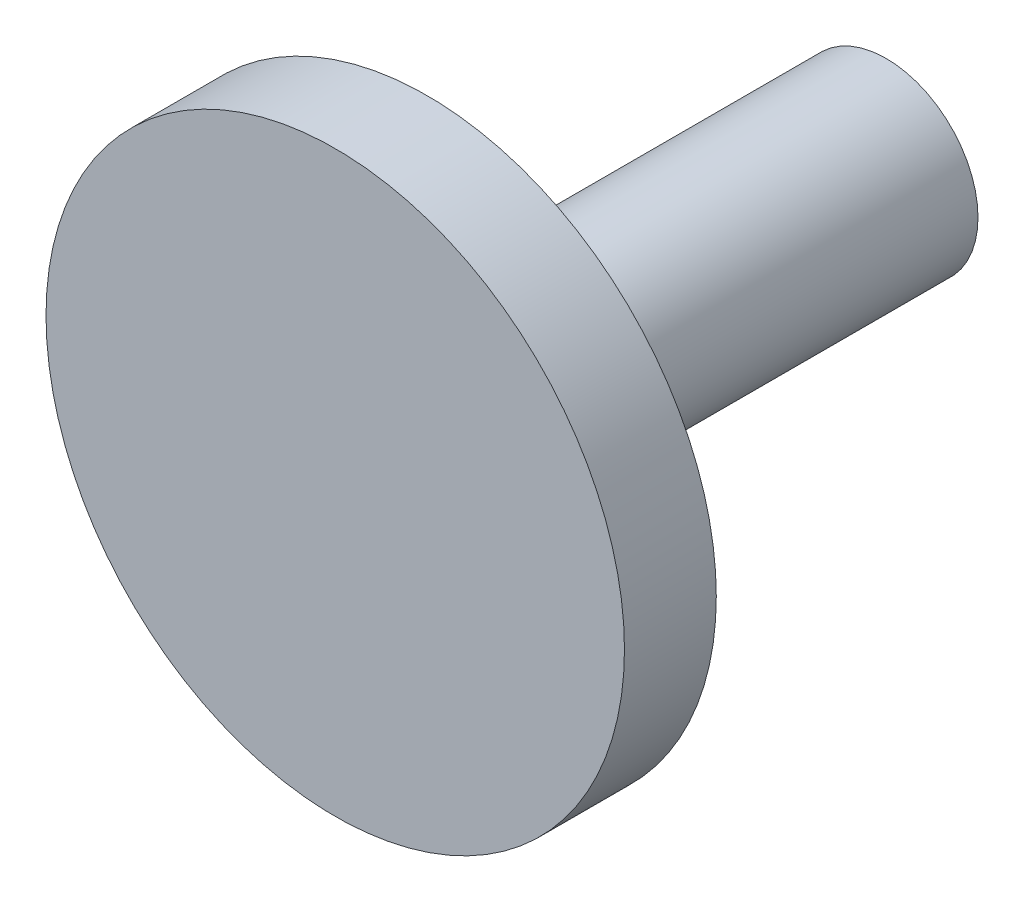
SolidWorks part; units mm, degrees
ref_plane "Front Plane" through (0, 0, 0) normal (0, 0, 1) x (1, 0, 0)
ref_plane "Top Plane" through (0, 0, 0) normal (0, 1, 0) x (1, 0, 0)
ref_plane "Right Plane" through (0, 0, 0) normal (1, 0, 0) x (0, 0, -1)
sketch "Sketch1" plane through (0, 0, 0) normal (0, 0, 1) x (1, 0, 0)
  circle A0 centre (0, 0) radius 15.75
  circle A1 centre (0, 0) radius 5
  dimension "D1" = 31.5
  dimension "D2" = 10
extrude "Boss-Extrude1" add sketch "Sketch1" along normal blind 5 contours A0
extrude "Boss-Extrude2" add sketch "Sketch1<3>" against normal blind 25 contours A1
sketch "Sketch1<3>" plane through (0, 0, 0) normal (0, 0, 1) x (1, 0, 0) same geometry as "Sketch1"
